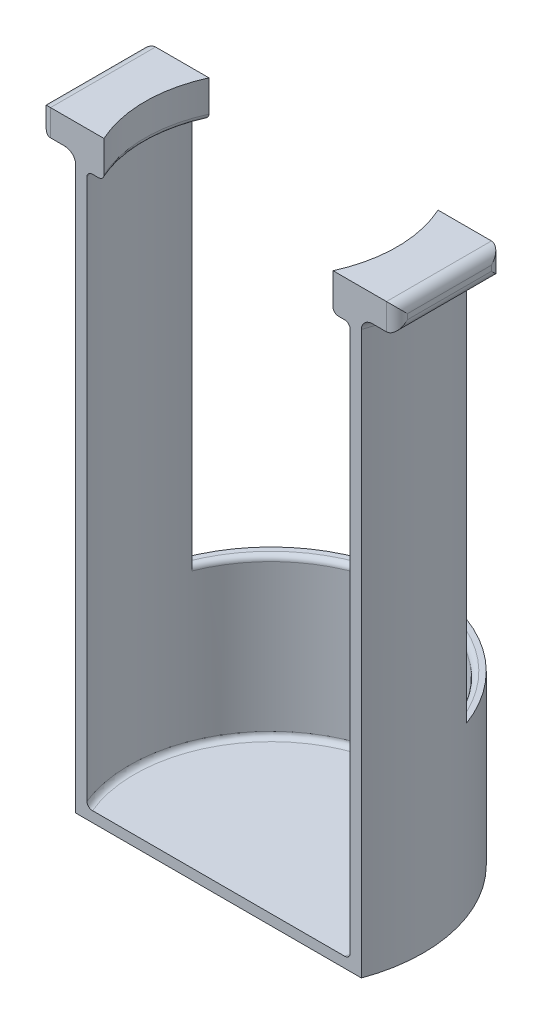
SolidWorks part; units mm, degrees
material "PLA+"
ref_plane "Front Plane" through (0, 0, 0) normal (0, 0, 1) x (1, 0, 0)
ref_plane "Top Plane" through (0, 0, 0) normal (0, 1, 0) x (1, 0, 0)
ref_plane "Right Plane" through (0, 0, 0) normal (1, 0, 0) x (0, 0, -1)
sketch "Sketch1" plane through (0, 0, 0) normal (0, 1, 0) x (1, 0, 0)
  circle A0 centre (0, 0) radius 27
  circle A1 centre (0, 0) radius 29
  dimension "D1" = 54
  dimension "D2" = 2
extrude "Boss-Extrude1" add sketch "Sketch1" along normal blind 30
sketch "Sketch2" plane through (0, 0, 0) normal (0, -1, 0) x (1, 0, 0)
  circle A0 centre (0, 0) radius 29
extrude "Boss-Extrude2" add sketch "Sketch2" along normal blind 2
sketch "Sketch3" plane through (0, 30, 0) normal (0, 1, 0) x (1, 0, 0)
  line L1 (29, 10) -> (-29, 10)
  line L2 (29, 10) -> (29, -10)
  line L3 (29, -10) -> (-29, -10)
  line L4 (-29, 10) -> (-29, -10)
  line L5 (29, 10) -> (-29, -10) construction
  line L6 (29, -10) -> (-29, 10) construction
  circle A0 centre (0, 0) radius 29
  circle A1 centre (0, 0) radius 27
  circle M5 centre (0, 0) radius 29
  circle M6 centre (0, 0) radius 27
  dimension "D1" = 58
  dimension "D2" = 54
  dimension "D3" = 29
  dimension "D4" = 20
extrude "Boss-Extrude3" add sketch "Sketch3" along normal blind 75 contours L3 L1 M5 M6 | L3 L1 M6 M5 region at (27.3808, 30, 0) region at (-27.3808, 30, 0)
sketch "Sketch4" plane through (0, 105, 0) normal (0, 1, 0) x (1, 0, 0)
  line L0 (-25.0799, 10) -> (-27.2213, 10) construction
  line L1 (29, 10) -> (-29, 10)
  line L2 (29, 10) -> (29, -10)
  line L3 (29, -10) -> (-29, -10)
  line L4 (-29, 10) -> (-29, -10)
  line L5 (29, 10) -> (-29, -10) construction
  line L6 (29, -10) -> (-29, 10) construction
  circle A0 centre (0, 0) radius 29
  circle A1 centre (0, 0) radius 24
  point P10 (21.8174, 10)
  point P11 (27.2213, 10)
  point P12 (27.2213, -10)
  point P14 (21.8174, -10)
  line M4 (25.0799, -10) -> (27.2213, -10)
  arc M5 (27.2213, -10) -> (27.2213, 10) centre (0, 0) ccw
  line M6 (27.2213, 10) -> (25.0799, 10)
  arc M7 (25.0799, 10) -> (25.0799, -10) centre (0, 0) cw
  dimension "D1" = 58
  dimension "D4" = 5
  dimension "D2" = 29
  dimension "D3" = 0
extrude "Boss-Extrude5" add sketch "Sketch4" along normal blind 2 contours A1 L3 L1 M7 | M7 M4 M5 M6 | A1 L1 A0 L3 region at (27.3808, 105, 0) region at (24.8127, 105, 0) region at (-25.8369, 105, 0)
fillet "Fillet2" radius 1 7 edges at (0, 0, 27) (0, 30, -27) (0, 30, 27) (24, 105, 0) (-24, 105, 0) (-27, 105, 0) (27, 105, 0)
sketch "Sketch6" plane through (0, 107, 0) normal (0, 1, 0) x (1, 0, 0)
  line L0 (-21.8174, -10) -> (-27.2213, -10) construction
  line L1 (34, 10) -> (-34, 10)
  line L2 (34, 10) -> (34, -10)
  line L3 (34, -10) -> (-34, -10)
  line L4 (-34, 10) -> (-34, -10)
  line L5 (34, 10) -> (-34, -10) construction
  line L6 (34, -10) -> (-34, 10) construction
  arc A0 (-27.2213, 10) -> (-27.2213, -10) centre (0, 0) ccw construction
  circle A1 centre (0, 0) radius 24
  point P0 (0, 0)
  arc M4 (-21.8174, -10) -> (-21.8174, 10) centre (0, 0) cw
  line M5 (-21.8174, 10) -> (-27.2213, 10)
  arc M6 (-27.2213, 10) -> (-27.2213, -10) centre (0, 0) ccw
  line M7 (-27.2213, -10) -> (-21.8174, -10)
  dimension "D3" = 48
  dimension "D1" = 0
  dimension "D2" = 34
extrude "Boss-Extrude6" add sketch "Sketch6" along normal blind 5 contours L1 L4 L3 M6 | M7 M4 M5 M6 | A1 L3 L2 L1 region at (-25.8369, 107, 0) region at (-31.1823, 107, 0) region at (28.6236, 107, 0)
fillet "Fillet3" radius 2 10 edges at (-34, 109.5, 10) (-34, 109.5, -10) (34, 109.5, -10) (34, 109.5, 10) (34, 112, 0) (34, 107, 0) (-34, 112, 0) (-34, 107, 0) (29, 107, 0) (-29, 107, 0)
ref_plane "Plane1" through (0, 0, 29) normal (0, 0, 1) x (1, 0, 0)
sketch "Sketch7" plane through (0, 0, 29) normal (0, 0, 1) x (1, 0, 0)
  line L0 (-29, -2) -> (29, -2) construction
  line L1 (-35, 113) -> (35, 113)
  line L2 (-35, 113) -> (-35, -3)
  line L3 (-35, -3) -> (35, -3)
  line L4 (35, 113) -> (35, -3)
  line L5 (32, 112) -> (21.8174, 112) construction
  line L6 (34, 110) -> (34, 109) construction
  line L7 (-34, 109) -> (-34, 110) construction
  dimension "D1" = 1
  dimension "D2" = 1
  dimension "D3" = 1
  dimension "D4" = 1
extrude "Cut-Extrude1" cut sketch "Sketch7" against normal blind 19
